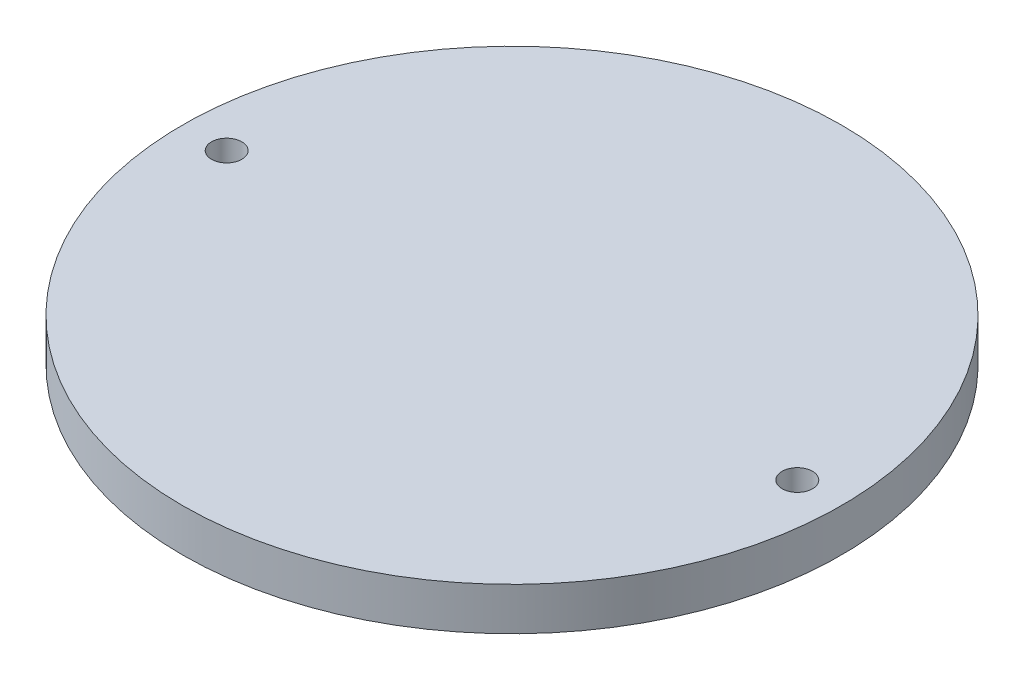
SolidWorks part; units mm, degrees
material "6061 Alloy"
ref_plane "Front Plane" through (0, 0, 0) normal (0, 0, 1) x (1, 0, 0)
ref_plane "Top Plane" through (0, 0, 0) normal (0, 1, 0) x (1, 0, 0)
ref_plane "Right Plane" through (0, 0, 0) normal (1, 0, 0) x (0, 0, -1)
sketch "Sketch2" plane through (0, 0, 0) normal (0, 1, 0) x (1, 0, 0)
  circle A0 centre (0, 0) radius 73.3425
  dimension "D1" = 146.685
extrude "Boss-Extrude1" add sketch "Sketch2" along normal blind 9.525
sketch "Sketch3" plane through (0, 9.525, 0) normal (0, 1, 0) x (1, 0, 0)
  point P0 (-63.5, 0)
  point P1 (63.5, 0)
  dimension "D1" = 63.5
  dimension "D2" = 63.5
hole_wizard "1/4 Clearance Hole1" positions "Sketch3" profile "Sketch4" hole size "1/4" standard "ANSI Inch" end condition through all
sketch "Sketch4" plane through (-63.5, 9.525, 0) normal (1, 0, 0) x (0, 0, 1)
  line L0 (0, 0) -> (0, 9.525)
  line L1 (0, 9.525) -> (3.3782, 9.525)
  line L2 (3.3782, 9.525) -> (3.3782, 0)
  line L5 (3.3782, 0) -> (0, 0)
  line L11 (0, -6.35) -> (0, 107.95) construction
  dimension "Thru Hole Dia." = 6.7564
  dimension "Thru Hole Depth" = 9.525
equation "\"outerdiameter\"= 5.775"
equation "\"D1@Sketch2\"=\"outerdiameter\""
equation "\"platethickness\"= 0.375"
equation "\"holespacing\"= 2.5"
equation "\"D1@Sketch3\"=\"holespacing\""
equation "\"D2@Sketch3\"=\"holespacing\""
